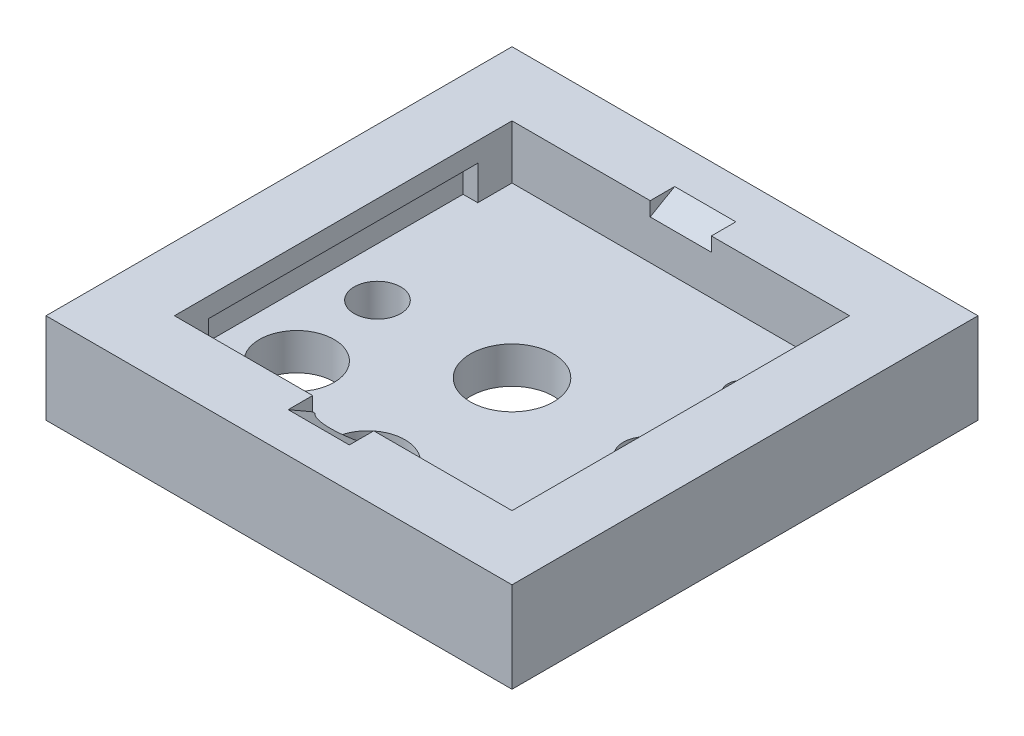
SolidWorks part; units mm, degrees
other "single-1350"
ref_plane "Front Plane" through (0, 0, 0) normal (0, 0, 1) x (1, 0, 0)
ref_plane "Top Plane" through (0, 0, 0) normal (0, 1, 0) x (1, 0, 0)
ref_plane "Right Plane" through (0, 0, 0) normal (1, 0, 0) x (0, 0, -1)
sketch "Sketch1" plane through (0, 0, 0) normal (0, 1, 0) x (1, 0, 0)
  line L0 (-6.9, 6.9) -> (6.9, 6.9)
  line L1 (6.9, 6.9) -> (6.9, -6.9)
  line L2 (6.9, -6.9) -> (1.1514, -6.9)
  line L3 (-6.9, -6.9) -> (-6.9, 6.9)
  line L4 (13.0003, 0) -> (-13.0003, 0) construction
  line L5 (0, 13.0493) -> (0, -13.0493) construction
  line L6 (-1.1514, -6.9) -> (-6.9, -6.9)
  line L8 (-9.525, -9.525) -> (9.525, -9.525)
  line L9 (-9.525, -9.525) -> (-9.525, 9.525)
  line L10 (-9.525, 9.525) -> (9.525, 9.525)
  line L11 (9.525, -9.525) -> (9.525, 9.525)
  line L12 (-9.525, -9.525) -> (9.525, 9.525) construction
  line L13 (-9.525, 9.525) -> (9.525, -9.525) construction
  circle A0 centre (0, 0) radius 1.7
  circle A1 centre (-5.5, 0) radius 0.95
  circle A2 centre (5.5, 0) radius 0.95
  circle A3 centre (-5, -3.8) radius 1.525
  circle A4 centre (0, -5.9) radius 1.525
  circle A5 centre (5.22, 4.2) radius 0.6
  point P20 (0, 0)
  point P23 (0, 0)
  dimension "D1" = 11
  dimension "D2" = 1.9
  dimension "D3" = 3.05
  dimension "D5" = 3.4
  dimension "D8" = 1.2
  dimension "D13" = 6.9
  dimension "D16" = 19.05
  dimension "D4" = 5
  dimension "D6" = 5.9
  dimension "D7" = 4.2
  dimension "D9" = 13.8
  dimension "D10" = 5.22
  dimension "D11" = 3.8
  dimension "D12" = 6.9
  dimension "D14" = 5.5
  dimension "D15" = 19.05
extrude "Boss-Extrude1" add sketch "Sketch1" along normal blind 3.7 contours L8 L11 L10 L9 A4 L6 L3 L0 L1 L2 | A4 L2 L1 L0 L3 L6 A5 A0 A1 A2 A3 region at (0, 0, -6.7048) region at (-9.2556, 0, 0)
extrude "Cut-Extrude1" cut sketch "Sketch1<3>" against normal blind 2.2 from surface contours A4 L2 L1 L0 L3 L6 A5 A0 A1 A2 A3 region at (0, 0, -6.7048) starting at face at (0, 3.7, 7.425)
sketch "Sketch1<3>" plane through (0, 0, 0) normal (0, 1, 0) x (1, 0, 0) same geometry as "Sketch1"
sketch "Sketch2" plane through (0, 0, 0) normal (1, 0, 0) x (0, 0, -1)
  line L0 (-7.9, 3.7) -> (-6.9, 3.7)
  line L1 (-6.9, 3.7) -> (-6.9, 3.1226)
  line L2 (-6.9, 3.1226) -> (-7.9, 3.7)
  line L3 (-6.9, 1.5) -> (-6.9, 3.7) construction
  dimension "D1" = 150
  dimension "D2" = 1
extrude "Cut-Extrude2" cut sketch "Sketch2" against normal mid plane 2.5
mirror "Mirror1" about plane through (0, 0, 0) normal (0, 0, 1) of "Cut-Extrude2"
sketch "Sketch4" plane through (0, 0, 0) normal (0, 0, 1) x (1, 0, 0)
  line L2 (-6.9, 2.9) -> (-6.9, 1.5)
  line L3 (-6.9, 1.5) -> (-7.5, 1.5)
  line L4 (-7.5, 2.8) -> (-7.5, 1.5)
  line L5 (-6.9, 3.7) -> (-7.5, 1.5) construction
  line L10 (-7.5, 2.8) -> (-7, 2.8)
  line L11 (-7, 2.8) -> (-6.9, 2.9)
  line L12 (-6.9, 3.7) -> (-6.9, 2.9) construction
  dimension "D1" = 0.9
  dimension "D2" = 0.6
  dimension "D4" = 45
  dimension "D5" = 0.5
extrude "Cut-Extrude3" cut sketch "Sketch4" against normal mid plane 11
mirror "Mirror2" about plane through (0, 0, 0) normal (1, 0, 0) of "Cut-Extrude3"
equation "\"key_spacing\"= 19.05mm"
